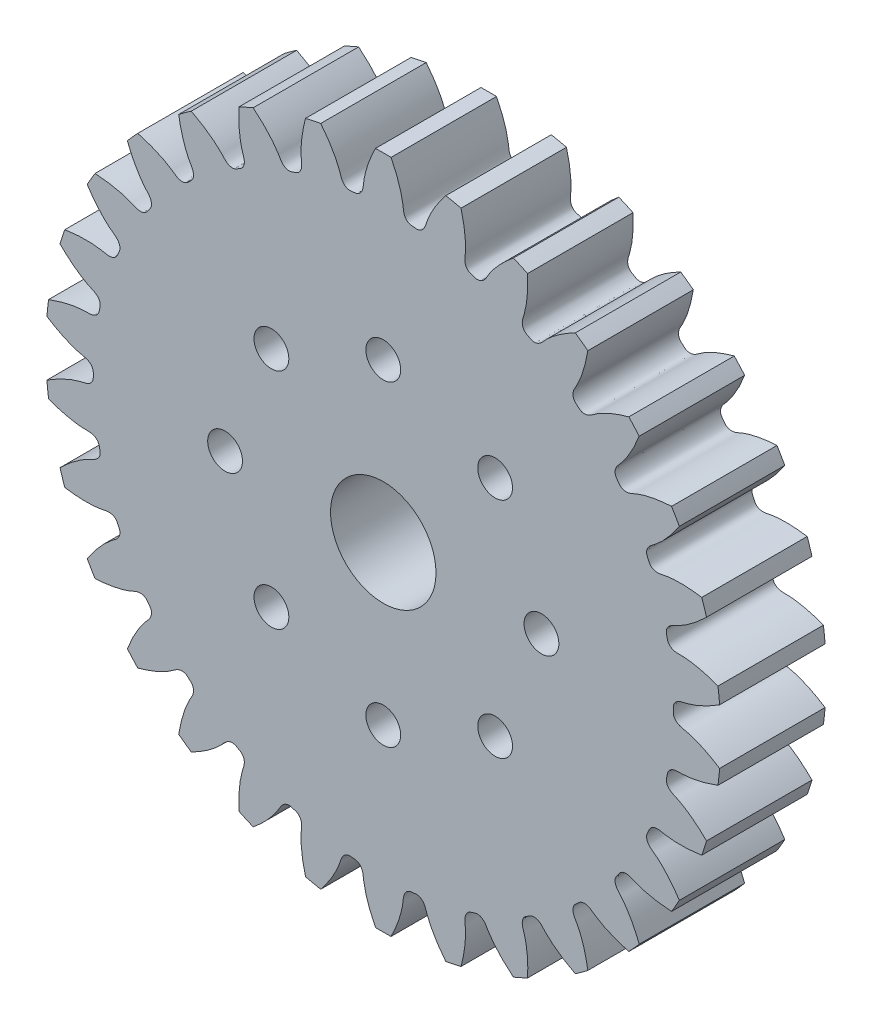
SolidWorks part; units mm, degrees
ref_plane "前视基准面" through (0, 0, 0) normal (0, 0, 1) x (1, 0, 0)
ref_plane "上视基准面" through (0, 0, 0) normal (0, 1, 0) x (1, 0, 0)
ref_plane "右视基准面" through (0, 0, 0) normal (1, 0, 0) x (0, 0, -1)
other "Configuration Table"
ref_axis "基准轴1" through (0, 0, 55) along (0, 0, -1)
sketch "SketchRevolveSpurGear1" plane through (0, 0, 0) normal (1, 0, 0) x (0, 0, -1)
  line L0 (0, 0) -> (1, 0) construction
  line L1 (-5, 0) -> (-5, 32)
  line L2 (-5, 32) -> (5, 32)
  line L3 (5, 32) -> (5, 0)
  line L4 (5, 0) -> (-5, 0)
revolve "SpurGear1" add sketch "SketchRevolveSpurGear1" angle 360 about L0
sketch "SketchToothSpurGear1" plane through (0, 0, 0) normal (0, 0, 1) x (1, 0, 0)
  arc A0 (31.9885, 2.6729) -> (31.9885, -2.6729) centre (0, 0) cw
  spline S0 degree 3 poles (31.9885, -2.6729) (31.6655, -2.4604) (31.2361, -2.2002) (30.6973, -1.9148) (30.407, -1.771) (30.1318, -1.6439) (29.8725, -1.5326) (29.6297, -1.436) (29.404, -1.3533) (29.1959, -1.2835) (29.0061, -1.2253) (28.8347, -1.1781) (28.5552, -1.1081) (28.2902, -1.0676) (28.0569, -0.9756) (27.9566, -0.9269) (27.8578, -0.8666) (27.7595, -0.7898) (27.6629, -0.6889) (27.5748, -0.555) (27.516, -0.3938) (27.4926, -0.2034) (27.5042, 0) (27.4926, 0.2034) (27.516, 0.3938) (27.5748, 0.555) (27.6629, 0.6889) (27.7595, 0.7898) (27.8578, 0.8666) (27.9566, 0.9269) (28.0569, 0.9756) (28.2902, 1.0676) (28.5552, 1.1081) (28.8347, 1.1781) (29.0061, 1.2253) (29.1959, 1.2835) (29.404, 1.3533) (29.6297, 1.436) (29.8725, 1.5326) (30.1318, 1.6439) (30.407, 1.771) (30.6973, 1.9148) (31.2361, 2.2002) (31.6655, 2.4604) (31.9885, 2.6729) knots 0 0 0 0 0.105026 0.136252 0.165585 0.193026 0.218574 0.24223 0.263994 0.283865 0.301843 0.317929 0.332123 0.380161 0.390132 0.400121 0.410437 0.42151 0.433904 0.448219 0.464748 0.480018 0.5 0.519982 0.535252 0.551781 0.566096 0.57849 0.589563 0.599879 0.609868 0.619839 0.667877 0.682071 0.698157 0.716135 0.736006 0.75777 0.781426 0.806974 0.834415 0.863748 0.894974 1 1 1 1
extrude "ToothExtrudeCutSpurGear1" cut sketch "SketchToothSpurGear1" against normal blind 5 and the other way blind 5
pattern_circular "PatternSpurGear1" count 30 every 12 about axis through (0, 0, 55) along (0, 0, -1) of "ToothExtrudeCutSpurGear1"
sketch "BoreRevolveSketch" plane through (0, 0, 0) normal (1, 0, 0) x (0, 0, -1)
  line L0 (0, 0) -> (1, 0) construction
  line L1 (-5, 0) -> (5, 0)
  line L2 (5, 0) -> (5, 5)
  line L3 (5, 5) -> (-5, 5)
  line L4 (-5, 5) -> (-5, 0)
  dimension "TaperSide1" = 5
  dimension "TaperSide2" = 5
revolve "BoreRevolveCut" cut sketch "BoreRevolveSketch" angle 360 about L0
sketch "AuxiliarySketchSpurGear1" plane through (0, 0, 0) normal (0, 0, 1) x (1, 0, 0)
  circle A0 centre (0, 0) radius 30 construction
  circle A1 centre (0, 0) radius 28.1908 construction
  circle A2 centre (0, 0) radius 28.4881 construction
  circle A3 centre (0, 0) radius 32 construction
  circle A4 centre (0, 0) radius 27.5 construction
  dimension "PitchDiameter" = 60
  dimension "BaseDiameter" = 56.3816
  dimension "FormDiameter" = 56.9763
  dimension "MajorDiameter" = 64
  dimension "MinorDiameter" = 55
sketch "草图5" plane through (0, 0, 5) normal (0, 0, 1) x (1, 0, 0)
  circle A1 centre (0, 15) radius 1.65
  circle A2 centre (10.6066, 10.6066) radius 1.65
  circle A3 centre (15, 0) radius 1.65
  circle A4 centre (10.6066, -10.6066) radius 1.65
  circle A5 centre (0, -15) radius 1.65
  circle A6 centre (-10.6066, -10.6066) radius 1.65
  circle A7 centre (-15, 0) radius 1.65
  circle A8 centre (-10.6066, 10.6066) radius 1.65
  point P21 (0, 0)
  dimension "D2" = 3.3
  dimension "D3" = 8
extrude "切除-拉伸2" cut sketch "草图5" against normal blind 10
